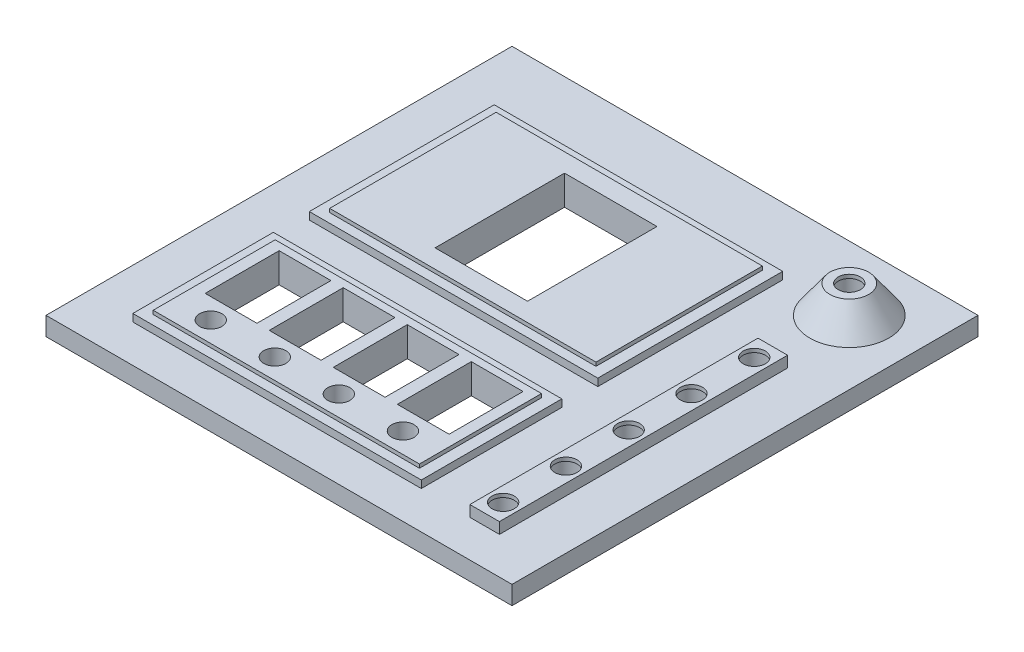
SolidWorks part; units mm, degrees
ref_plane "Front Plane" through (0, 0, 0) normal (0, 0, 1) x (1, 0, 0)
ref_plane "Top Plane" through (0, 0, 0) normal (0, 1, 0) x (1, 0, 0)
ref_plane "Right Plane" through (0, 0, 0) normal (1, 0, 0) x (0, 0, -1)
sketch "Sketch1" plane through (0, 0, 0) normal (0, 1, 0) x (1, 0, 0)
  line L1 (0, 0) -> (126, 0)
  line L2 (0, 0) -> (0, 126)
  line L3 (0, 126) -> (126, 126)
  line L4 (126, 0) -> (126, 126)
  dimension "D1" = 126
  dimension "D2" = 126
extrude "Boss-Extrude1" add sketch "Sketch1" along normal blind 5
sketch "Sketch3" plane through (0, 5, 0) normal (0, 1, 0) x (1, 0, 0)
  line L0 (108.6, 121.1) -> (108.6, 96.1) construction
  circle A0 centre (108.6, 108.6) radius 12.5
extrude "Boss-Extrude2" add sketch "Sketch3" along normal blind 7.5
sketch "Sketch4" plane through (0, 0, 0) normal (0, -1, 0) x (1, 0, 0)
  circle A1 centre (108.6, -108.6) radius 3.45
  dimension "D1" = 6.9
extrude "Cut-Extrude1" cut sketch "Sketch4" against normal blind 11.5
sketch "Sketch6" plane through (0, 12.5, 0) normal (0, 1, 0) x (1, 0, 0)
  line L0 (108.6, 121.1) -> (108.6, 96.1) construction
  circle A0 centre (108.6, 108.6) radius 12.5 construction
  circle A1 centre (108.6, 108.6) radius 3
  dimension "D1" = 6
extrude "Cut-Extrude2" cut sketch "Sketch6" against normal through all
chamfer "Chamfer1" distance 10 angle 36 1 edges at (108.6, 12.5, -96.1) first distance on face at (108.6, 12.5, -96.1)
sketch "Sketch7" plane through (0, 5, 0) normal (0, 1, 0) x (1, 0, 0)
  line L1 (0, 0) -> (126, 0) construction
  line L11 (108.6, 97.9164) -> (108.6, 0) construction
  line L12 (112.6, 10) -> (104.6, 10)
  line L13 (112.6, 10) -> (112.6, 87.9164)
  line L14 (112.6, 87.9164) -> (104.6, 87.9164)
  line L15 (104.6, 10) -> (104.6, 87.9164)
  line L16 (112.6, 10) -> (104.6, 87.9164) construction
  line L17 (112.6, 87.9164) -> (104.6, 10) construction
  circle A0 centre (108.6, 108.6) radius 10.6836 construction
  point P0 (108.6, 48.9582)
  dimension "D3" = 8
extrude "Boss-Extrude3" add sketch "Sketch7" along normal blind 3
sketch "Sketch8" plane through (0, 8, 0) normal (0, 1, 0) x (1, 0, 0)
  line L0 (108.6, 87.9164) -> (108.6, 10) construction
  line L1 (112.6, 87.9164) -> (104.6, 87.9164) construction
  line L2 (104.6, 10) -> (112.6, 10) construction
  line L9 (112.6, 87.9164) -> (104.6, 87.9164)
  line L10 (112.6, 87.9164) -> (112.6, 85.9164)
  line L12 (104.6, 87.9164) -> (104.6, 85.9164)
  circle A0 centre (108.6, 15) radius 3
  circle A1 centre (108.6, 31.9748) radius 3
  circle A2 centre (108.6, 48.9496) radius 3
  circle A3 centre (108.6, 65.9244) radius 3
  circle A4 centre (108.6, 82.8992) radius 3
  dimension "D3" = 6
  dimension "D1" = 5
  dimension "D2" = 2
extrude "Cut-Extrude3" cut sketch "Sketch8" against normal through all contours A4 | A3 | A2 | A1 | A0
sketch "Sketch9" plane through (0, 0, 0) normal (0, -1, 0) x (1, 0, 0)
  line L0 (108.6, -85.8992) -> (108.6, -12) construction
  circle A0 centre (108.6, -82.8992) radius 3 construction
  circle A1 centre (108.6, -15) radius 3 construction
  circle A2 centre (108.6, -82.8992) radius 3.45
  circle A3 centre (108.6, -65.9244) radius 3.45
  circle A4 centre (108.6, -48.9496) radius 3.45
  circle A5 centre (108.6, -15) radius 3.45
  circle A6 centre (108.6, -31.9748) radius 3.45
  dimension "D1" = 6.9
  dimension "D2" = 6.9
  dimension "D3" = 6.9
  dimension "D4" = 6.9
  dimension "D5" = 6.9
extrude "Cut-Extrude4" cut sketch "Sketch9" against normal blind 7
sketch "Sketch12" plane through (0, 5, 0) normal (0, 1, 0) x (1, 0, 0)
  line L4 (91.3, 107.8992) -> (13.3, 107.8992)
  line L5 (91.3, 107.8992) -> (91.3, 57.8992)
  line L6 (91.3, 57.8992) -> (13.3, 57.8992)
  line L7 (13.3, 107.8992) -> (13.3, 57.8992)
  line L8 (91.3, 107.8992) -> (13.3, 57.8992) construction
  line L9 (91.3, 57.8992) -> (13.3, 107.8992) construction
  line L14 (91.3, 10.1748) -> (13.3, 10.1748)
  line L15 (91.3, 10.1748) -> (91.3, 48.1748)
  line L16 (91.3, 48.1748) -> (13.3, 48.1748)
  line L17 (13.3, 10.1748) -> (13.3, 48.1748)
  line L18 (91.3, 10.1748) -> (13.3, 48.1748) construction
  line L19 (91.3, 48.1748) -> (13.3, 10.1748) construction
  point P0 (52.3, 82.8992)
  point P18 (52.3, 29.1748)
  dimension "D1" = 50
  dimension "D2" = 78
  dimension "D3" = 38
  dimension "D4" = 78
extrude "Boss-Extrude4" add sketch "Sketch12" along normal blind 2
sketch "Sketch13" plane through (0, 7, 0) normal (0, 1, 0) x (1, 0, 0)
  line L0 (52.3, 107.8992) -> (52.3, 57.8992) construction
  line L1 (91.3, 107.8992) -> (13.3, 107.8992) construction
  line L2 (13.3, 57.8992) -> (91.3, 57.8992) construction
  line L4 (88.3, 105.3992) -> (16.3, 105.3992)
  line L5 (88.3, 105.3992) -> (88.3, 60.3992)
  line L6 (88.3, 60.3992) -> (16.3, 60.3992)
  line L7 (16.3, 105.3992) -> (16.3, 60.3992)
  line L8 (88.3, 105.3992) -> (16.3, 60.3992) construction
  line L9 (88.3, 60.3992) -> (16.3, 105.3992) construction
  point P6 (52.3, 82.8992)
  dimension "D1" = 72
  dimension "D2" = 45
extrude "Boss-Extrude5" add sketch "Sketch13" along normal blind 1
sketch "Sketch14" plane through (0, 7, 0) normal (0, 1, 0) x (1, 0, 0)
  line L0 (52.3, 48.1748) -> (52.3, 10.1748) construction
  line L1 (91.3, 48.1748) -> (13.3, 48.1748) construction
  line L2 (13.3, 10.1748) -> (91.3, 10.1748) construction
  line L3 (16.3, 60.3992) -> (16.3, 10.1748) construction
  line L4 (88.3, 60.3992) -> (88.3, 10.1748) construction
  line L6 (88.3, 45.6748) -> (16.3, 45.6748)
  line L7 (88.3, 45.6748) -> (88.3, 12.6748)
  line L8 (88.3, 12.6748) -> (16.3, 12.6748)
  line L9 (16.3, 45.6748) -> (16.3, 12.6748)
  line L10 (88.3, 45.6748) -> (16.3, 12.6748) construction
  line L11 (88.3, 12.6748) -> (16.3, 45.6748) construction
  point P12 (52.3, 29.1748)
  dimension "D1" = 33
extrude "Boss-Extrude6" add sketch "Sketch14" along normal blind 1
sketch "Sketch17" plane through (0, 8, 0) normal (0, 1, 0) x (1, 0, 0)
  line L0 (52.3, 105.3992) -> (52.3, 60.3992) construction
  line L1 (88.3, 105.3992) -> (16.3, 105.3992) construction
  line L2 (16.3, 60.3992) -> (88.3, 60.3992) construction
  line L4 (64.8, 100.3992) -> (39.8, 100.3992)
  line L5 (64.8, 100.3992) -> (64.8, 65.3992)
  line L6 (64.8, 65.3992) -> (39.8, 65.3992)
  line L7 (39.8, 100.3992) -> (39.8, 65.3992)
  line L8 (64.8, 100.3992) -> (39.8, 65.3992) construction
  line L9 (64.8, 65.3992) -> (39.8, 100.3992) construction
  point P6 (52.3, 82.8992)
  dimension "D1" = 25
  dimension "D2" = 35
extrude "Cut-Extrude6" cut sketch "Sketch17" against normal through all
sketch "Sketch18" plane through (0, 8, 0) normal (0, 1, 0) x (1, 0, 0)
  line L0 (36.7018, 43.6585) -> (36.7018, 23.6585)
  line L5 (54.0199, 43.6585) -> (54.0199, 23.6585)
  line L6 (71.338, 43.6585) -> (71.338, 23.6585)
  line L12 (50.7018, 43.6585) -> (36.7018, 43.6585)
  line L13 (33.3837, 43.6585) -> (19.3837, 43.6585)
  line L14 (33.3837, 43.6585) -> (33.3837, 23.6585)
  line L15 (33.3837, 23.6585) -> (19.3837, 23.6585)
  line L16 (19.3837, 43.6585) -> (19.3837, 23.6585)
  line L17 (33.3837, 43.6585) -> (19.3837, 23.6585) construction
  line L18 (33.3837, 23.6585) -> (19.3837, 43.6585) construction
  line L19 (50.7018, 43.6585) -> (50.7018, 23.6585)
  line L20 (50.7018, 23.6585) -> (36.7018, 23.6585)
  line L22 (50.7018, 43.6585) -> (36.7018, 23.6585) construction
  line L23 (50.7018, 23.6585) -> (36.7018, 43.6585) construction
  line L24 (68.0199, 43.6585) -> (54.0199, 43.6585)
  line L25 (68.0199, 43.6585) -> (68.0199, 23.6585)
  line L26 (68.0199, 23.6585) -> (54.0199, 23.6585)
  line L28 (68.0199, 43.6585) -> (54.0199, 23.6585) construction
  line L29 (68.0199, 23.6585) -> (54.0199, 43.6585) construction
  line L30 (85.338, 43.6585) -> (71.338, 43.6585)
  line L31 (85.338, 43.6585) -> (85.338, 23.6585)
  line L32 (85.338, 23.6585) -> (71.338, 23.6585)
  line L34 (85.338, 43.6585) -> (71.338, 23.6585) construction
  line L35 (85.338, 23.6585) -> (71.338, 43.6585) construction
  point P1 (0, 0)
  point P17 (26.3837, 33.6585)
  dimension "D3" = 14
  dimension "D4" = 20
  dimension "D5" = 4
extrude "Cut-Extrude7" cut sketch "Sketch18" against normal through all
sketch "Sketch19" plane through (0, 8, 0) normal (0, 1, 0) x (1, 0, 0)
  line L2 (16.3, 12.6748) -> (88.3, 12.6748) construction
  line L9 (26.3837, 23.6585) -> (26.3837, 12.6748) construction
  line L10 (19.3837, 23.6585) -> (33.3837, 23.6585) construction
  line L11 (43.7018, 12.6748) -> (43.7018, 23.6585) construction
  line L12 (61.0199, 23.6585) -> (61.0199, 12.6748) construction
  line L13 (54.0199, 23.6585) -> (68.0199, 23.6585) construction
  line L14 (78.338, 23.6585) -> (78.338, 12.6748) construction
  line L15 (71.338, 23.6585) -> (85.338, 23.6585) construction
  circle A0 centre (26.3837, 18.1667) radius 3
  circle A1 centre (43.7018, 18.1667) radius 3
  circle A2 centre (61.0199, 18.1667) radius 3
  circle A3 centre (78.338, 18.1667) radius 3
  dimension "D1" = 6
  dimension "D2" = 6
  dimension "D3" = 6
  dimension "D4" = 6
extrude "Cut-Extrude8" cut sketch "Sketch19" against normal through all
